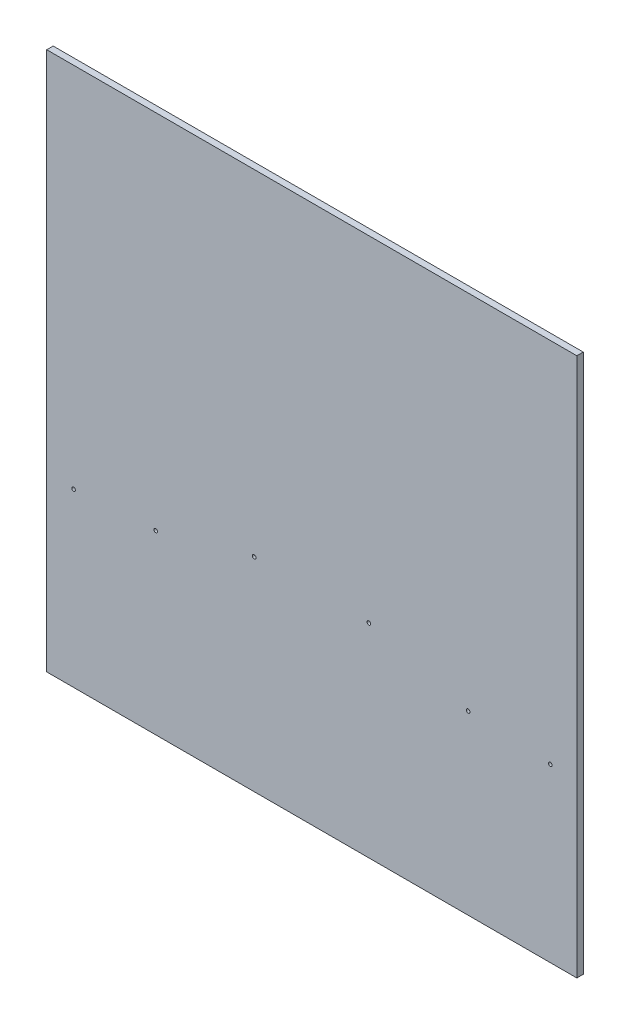
SolidWorks part; units mm, degrees
material "Pine"
ref_plane "Front Plane" through (0, 0, 0) normal (0, 0, 1) x (1, 0, 0)
ref_plane "Top Plane" through (0, 0, 0) normal (0, 1, 0) x (1, 0, 0)
ref_plane "Right Plane" through (0, 0, 0) normal (1, 0, 0) x (0, 0, -1)
sketch "Sketch1" plane through (0, 0, 0) normal (0, 0, 1) x (1, 0, 0)
  line L0 (751.2336, -529.2906) -> (-410.1935, -529.2906) construction
  line L1 (-232.0004, 467.6594) -> (751.2336, 467.6594)
  line L2 (-232.0004, 467.6594) -> (-232.0004, -529.2906)
  line L4 (751.2336, 467.6594) -> (751.2336, -529.2906)
  line L6 (751.2336, -529.2906) -> (751.2336, -531.8306)
  line L7 (751.2336, -531.8306) -> (-232.0004, -531.8306)
  line L8 (-232.0004, -529.2906) -> (-232.0004, -531.8306)
  dimension "D1" = 983.234
  dimension "D2" = 996.95
  dimension "D3" = 2.54
  dimension "D4" = 999.49
extrude "Boss-Extrude1" add sketch "Sketch1" along normal blind 11.9062
hole_wizard "CSK for 1/4 Flat Head Machine Screw1" positions "3DSketch1" profile "Sketch2" countersink size "1/4" standard "ANSI Inch" end condition through all
sketch3d "3DSketch1"
  line L3 (751.2336, -531.8306, 0) -> (751.2336, 467.6594, 0) construction
  line L4 (-232.0004, -529.2098, 0) -> (797.0179, -529.2098, 0) construction
  line L5 (-232.0004, 467.6594, 0) -> (-232.0004, -531.8306, 0) construction
  line L7 (-232.0004, -531.8306, 0) -> (751.2336, -531.8306, 0) construction
  line L8 (282.5087, -529.2098, 0) -> (282.5087, 105.8303, 0) construction
  point P0 (702.0211, -213.2973, 0)
  point P2 (549.6211, -203.7723, 0)
  point P4 (365.4711, -154.5598, 0)
  point P6 (152.7461, -154.5598, 0)
  point P8 (-29.8164, -203.7723, 0)
  point P10 (-182.2164, -213.2973, 0)
  dimension "D2" = 315.9125
  dimension "D3" = 325.4375
  dimension "D11" = 374.65
  dimension "D4" = 49.2125
  dimension "D5" = 201.6125
  dimension "D6" = 385.7625
  dimension "D7" = 598.4875
  dimension "D8" = 781.05
  dimension "D9" = 933.45
  dimension "D10" = 2.6208
  dimension "D12" = 2.6208
sketch "Sketch2" plane through (702.0211, -213.2973, 0) normal (1, 0, 0) x (0, 1, 0)
  line L0 (0, 0) -> (0, 11.9062)
  line L1 (0, 11.9062) -> (3.3782, 11.9062)
  line L2 (3.3782, 11.9062) -> (3.3782, 3.5209)
  line L3 (3.3782, 3.5209) -> (6.4389, 0)
  line L5 (6.4389, 0) -> (0, 0)
  line L6 (-3.3782, 3.5209) -> (-6.4389, 0) construction
  line L11 (0, -6.35) -> (0, 107.95) construction
  dimension "Thru Hole Dia." = 6.7564
  dimension "Thru Hole Depth" = 11.9062
  dimension "Near C'Sink Dia." = 12.8778
  dimension "Near C'Sink Angle" = 82
